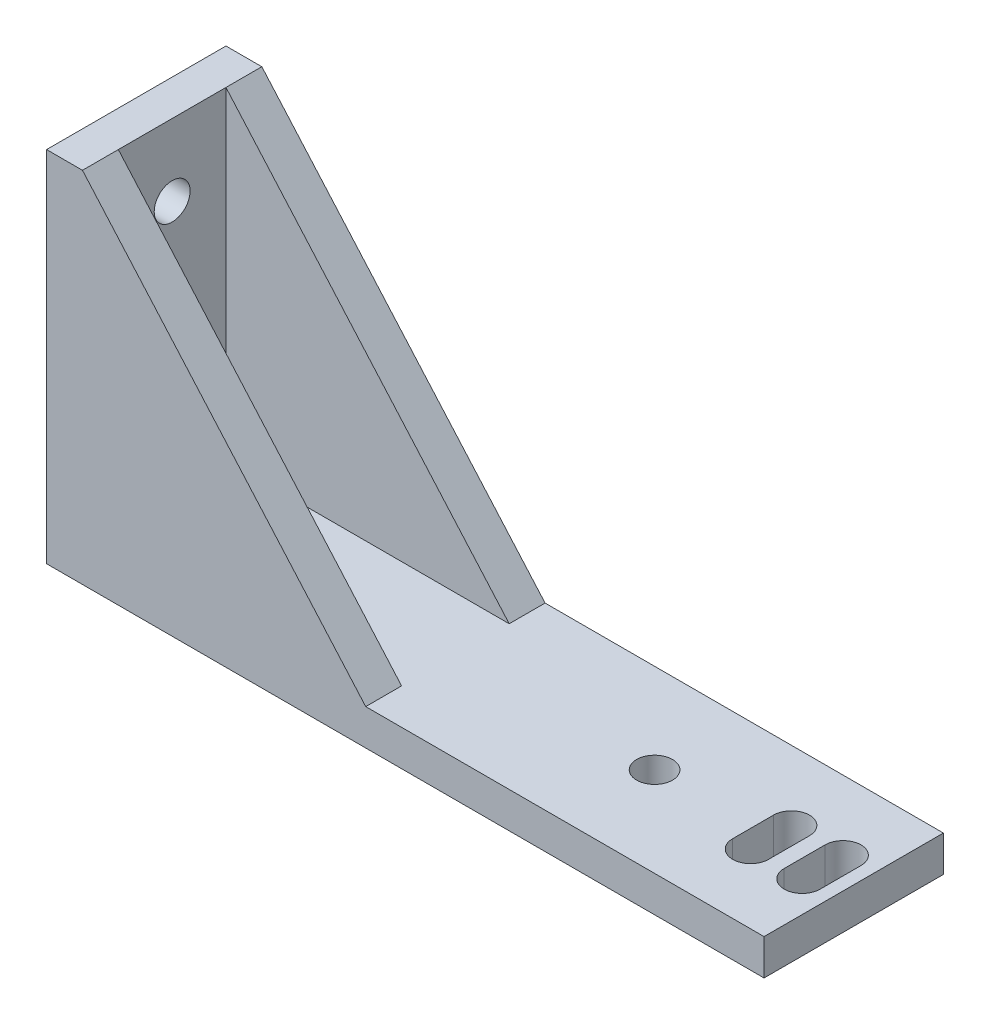
SolidWorks part; units mm, degrees
ref_plane "Front Plane" through (0, 0, 0) normal (0, 0, 1) x (1, 0, 0)
ref_plane "Top Plane" through (0, 0, 0) normal (0, 1, 0) x (1, 0, 0)
ref_plane "Right Plane" through (0, 0, 0) normal (1, 0, 0) x (0, 0, -1)
sketch "Sketch1" plane through (0, 0, 0) normal (0, 1, 0) x (1, 0, 0)
  line L1 (-53.3412, 17.0332) -> (46.6588, 17.0332)
  line L2 (-53.3412, 17.0332) -> (-53.3412, 2.0332)
  line L3 (-53.3412, 2.0332) -> (46.6588, 2.0332)
  line L4 (46.6588, 17.0332) -> (46.6588, 2.0332)
  dimension "D1" = 100
  dimension "D2" = 15
extrude "Boss-Extrude1" add sketch "Sketch1" along normal blind 5
sketch "Sketch2" plane through (0, 5, 0) normal (0, 1, 0) x (1, 0, 0)
  line L0 (-53.3412, 17.0332) -> (-48.3412, 17.0332)
  line L1 (46.6588, 17.0332) -> (-53.3412, 17.0332) construction
  line L2 (-53.3412, 2.0332) -> (-48.3412, 2.0332)
  line L3 (-53.3412, 2.0332) -> (46.6588, 2.0332) construction
  line L4 (-48.3412, 17.0332) -> (-48.3412, 2.0332)
  line L5 (-53.3412, 17.0332) -> (-53.3412, 2.0332)
extrude "Boss-Extrude2" add sketch "Sketch2" along normal blind 45
sketch "Sketch3" plane through (0, 0, 0) normal (0, -1, 0) x (-1, 0, 0)
  line L0 (53.3412, 2.0332) -> (1.3612, 2.0332) construction
  line L1 (53.3412, 2.0332) -> (-46.6588, 2.0332) construction
  line L2 (1.3612, 2.0332) -> (1.3612, -8.4668) construction
  line L3 (8.8612, 17.0332) -> (8.8612, 22.0332)
  line L5 (-46.6588, 17.0332) -> (53.3412, 17.0332) construction
  line L6 (8.8612, 22.0332) -> (-46.6588, 22.0332)
  line L8 (-46.6588, 22.0332) -> (-46.6588, 17.0332)
  line L9 (-46.6588, 17.0332) -> (8.8612, 17.0332)
  line L15 (1.3612, 2.0332) -> (8.8612, 2.0332)
  line L16 (1.3612, 2.0332) -> (-46.6588, 2.0332)
  line L17 (8.8612, 2.0332) -> (8.8612, -2.9668)
  line L18 (-46.6588, 2.0332) -> (-46.6588, -2.9668)
  line L19 (-46.6588, -2.9668) -> (8.8612, -2.9668)
  point P13 (-17.293, 2.0332)
  point P16 (-46.6588, 2.0332)
  line M5 (53.3412, 17.0332) -> (-46.6588, 17.0332)
  line M7 (-46.6588, 2.0332) -> (53.3412, 2.0332)
extrude "Boss-Extrude3" add sketch "Sketch3" against normal blind 5 contours L8 L6 M5 | L19 M7 region at (18.8988, 0, -19.5332) region at (18.8988, 0, 0.4668)
sketch "Sketch4" plane through (0, 0, 0) normal (0, -1, 0) x (-1, 0, 0)
  line L0 (-46.6588, 9.5332) -> (53.3412, 9.5332)
  line L1 (-46.6588, -2.9668) -> (-46.6588, 22.0332) construction
  line L2 (53.3412, 17.0332) -> (53.3412, 2.0332) construction
sketch "Sketch5" plane through (-53.3412, 0, 0) normal (-1, 0, 0) x (0, 0, 1)
  line L0 (-9.5332, 0) -> (-9.5332, 15)
  line L1 (-17.0332, 0) -> (-2.0332, 0) construction
  line L2 (-9.5332, 50) -> (-9.5332, 40)
  line L3 (-17.0332, 50) -> (-2.0332, 50) construction
  point P8 (-9.5332, 34.9287)
hole_wizard "Ø5.0mm Dowel Slot1" positions "Sketch6" profile "Sketch7" size "Ø5.0" standard "ANSI Metric" slot yes end condition up to next
sketch "Sketch6" plane through (0, 5, 0) normal (0, 1, 0) x (1, 0, 0)
  line L0 (42.3428, 4.1592) -> (42.3428, 14.8592) construction
  point P0 (42.3428, 9.5092)
  point P5 (0, 0)
  dimension "D1" = 10.7
sketch "Sketch7" plane through (42.3428, 5, -9.5092) normal (1, 0, 0) x (0, 0, 1)
  line L0 (0, 0) -> (0, 5)
  line L1 (0, 5) -> (2.5, 5)
  line L2 (2.5, 5) -> (2.5, 0)
  line L5 (2.5, 0) -> (0, 0)
  line L11 (0, -6.35) -> (0, 107.95) construction
  dimension "Thru Hole Dia." = 5
  dimension "Thru Hole Depth" = 5
hole_wizard "Ø5.0mm Dowel Slot2" positions "Sketch8" profile "Sketch9" size "Ø5.0" standard "ANSI Metric" slot yes end condition up to next
sketch "Sketch8" plane through (0, 0, 0) normal (0, -1, 0) x (-1, 0, 0)
  line L0 (-35.1546, 4.1648) -> (-35.1546, 14.8648) construction
  point P0 (-35.1546, 9.5148)
  point P5 (0, 0)
  dimension "D1" = 10.7
sketch "Sketch9" plane through (35.1546, 0, -9.5148) normal (1, 0, 0) x (0, 0, -1)
  line L0 (0, 0) -> (0, 5)
  line L1 (0, 5) -> (2.5, 5)
  line L2 (2.5, 5) -> (2.5, 0)
  line L5 (2.5, 0) -> (0, 0)
  line L11 (0, -6.35) -> (0, 107.95) construction
  dimension "Thru Hole Dia." = 5
  dimension "Thru Hole Depth" = 5
hole_wizard "Ø5.0mm Dowel Hole1" positions "Sketch10" profile "Sketch11" hole size "Ø5.0" standard "ANSI Metric" end condition up to next
sketch "Sketch10" plane through (-53.3412, 0, 0) normal (-1, 0, 0) x (0, 0, 1)
  point P0 (-9.5332, 40)
  point P3 (-9.9586, 15)
  point P6 (0, 0)
  point P7 (0, 0)
  point P8 (0, 0)
  point P9 (-9.5332, 40)
sketch "Sketch11" plane through (-53.3412, 40, -9.5332) normal (0, 1, 0) x (0, 0, 1)
  line L0 (0, 0) -> (0, 5)
  line L1 (0, 5) -> (2.5, 5)
  line L2 (2.5, 5) -> (2.5, 0)
  line L5 (2.5, 0) -> (0, 0)
  line L11 (0, -6.35) -> (0, 107.95) construction
  dimension "Thru Hole Dia." = 5
  dimension "Thru Hole Depth" = 5
sketch "Sketch12" plane through (0, 5, 0) normal (0, 1, 0) x (1, 0, 0)
  line L0 (18.8988, 22.0332) -> (18.8988, -2.9668)
  line L1 (-8.8612, 22.0332) -> (46.6588, 22.0332) construction
  line L2 (46.6588, -2.9668) -> (-8.8612, -2.9668) construction
  line L3 (18.8988, -2.9668) -> (18.8988, 9.5332)
  line L4 (18.8988, 9.5332) -> (-8.8612, 9.5332)
hole_wizard "Ø5.0mm Dowel Hole2" positions "Sketch13" profile "Sketch14" hole size "Ø5.0" standard "ANSI Metric" end condition up to next
sketch "Sketch13" plane through (0, 5, 0) normal (0, 1, 0) x (1, 0, 0)
  point P0 (18.8988, 9.5332)
sketch "Sketch14" plane through (18.8988, 5, -9.5332) normal (1, 0, 0) x (0, 0, 1)
  line L0 (0, 0) -> (0, 5)
  line L1 (0, 5) -> (2.5, 5)
  line L2 (2.5, 5) -> (2.5, 0)
  line L5 (2.5, 0) -> (0, 0)
  line L11 (0, -6.35) -> (0, 107.95) construction
  dimension "Thru Hole Dia." = 5
  dimension "Thru Hole Depth" = 5
sketch "Sketch15" plane through (0, 0, -2.0332) normal (0, 0, 1) x (1, 0, 0)
  line L0 (-48.3412, 50) -> (-8.8612, 5)
  line L1 (-8.8612, 5) -> (-8.8612, 0)
  line L2 (-8.8612, 0) -> (-53.3412, 0)
  line L3 (-53.3412, 0) -> (-53.3412, 50)
  line L4 (-53.3412, 50) -> (-48.3412, 50)
extrude "Boss-Extrude4" add sketch "Sketch15" along normal blind 5
sketch "Sketch16" plane through (0, 0, -17.0332) normal (0, 0, -1) x (-1, 0, 0)
  line L0 (48.3412, 50) -> (8.8612, 5)
  line L1 (8.8612, 5) -> (8.8612, 0)
  line L2 (8.8612, 0) -> (53.3412, 0)
  line L3 (53.3412, 0) -> (53.3412, 50)
  line L4 (53.3412, 50) -> (48.3412, 50)
extrude "Boss-Extrude5" add sketch "Sketch16" along normal blind 5
